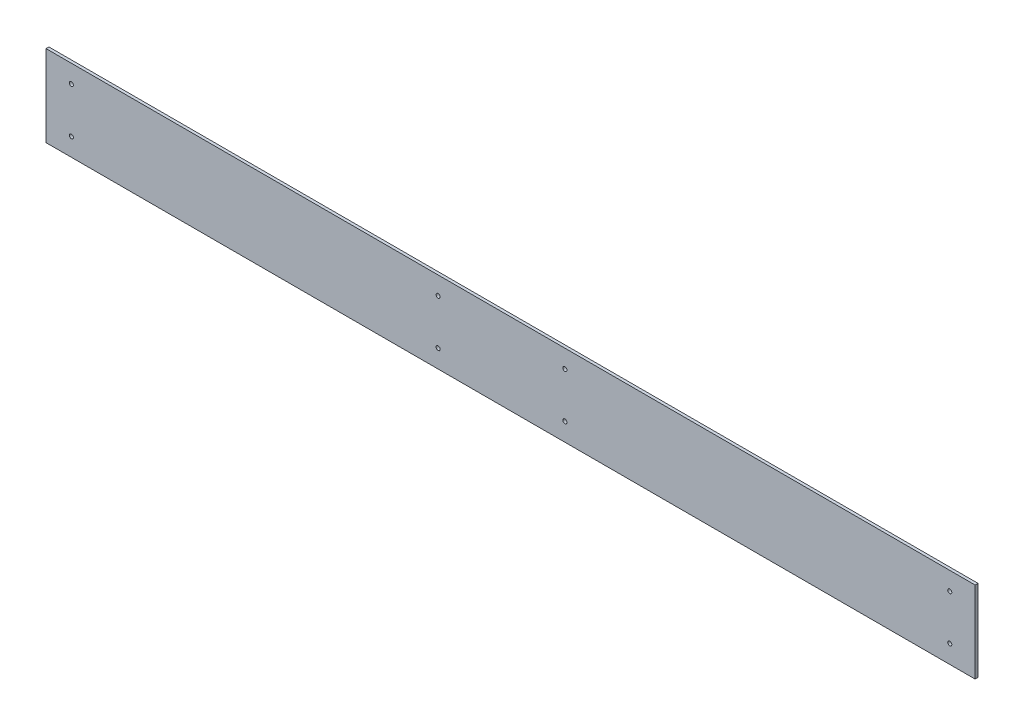
SolidWorks part; units mm, degrees
ref_plane "Front Plane" through (0, 0, 0) normal (0, 0, 1) x (1, 0, 0)
ref_plane "Top Plane" through (0, 0, 0) normal (0, 1, 0) x (1, 0, 0)
ref_plane "Right Plane" through (0, 0, 0) normal (1, 0, 0) x (0, 0, -1)
sketch "Sketch1" plane through (0, 0, 0) normal (0, 0, 1) x (1, 0, 0)
  line L1 (-513, -45) -> (513, -45)
  line L2 (-513, -45) -> (-513, 45)
  line L3 (-513, 45) -> (513, 45)
  line L4 (513, -45) -> (513, 45)
  line L5 (-513, -45) -> (513, 45) construction
  line L6 (-513, 45) -> (513, -45) construction
  point P0 (0, 0)
  dimension "D1" = 1026
  dimension "D2" = 90
extrude "Boss-Extrude1" add sketch "Sketch1" along normal blind 3.175
hole_wizard "M4 Clearance Hole1" positions "Sketch2" profile "Sketch4" hole size "M4" standard "ANSI Metric" end condition through all
sketch "Sketch2" plane through (0, 0, 3.175) normal (0, 0, 1) x (1, 0, 0)
  line L0 (-485, 25) -> (-485, -25)
  line L1 (513, 45) -> (-513, 45) construction
  line L2 (-513, -45) -> (513, -45) construction
  line L3 (-513, 45) -> (-513, -45) construction
  line L4 (0, -55) -> (0, 55) construction
  line L5 (485, 25) -> (485, -25)
  line L6 (-80, 25) -> (-80, -25)
  line L8 (60, 25) -> (60, -25)
  point P1 (-485, 25)
  point P2 (-485, -25)
  point P19 (485, -25)
  point P20 (485, 25)
  point P24 (-80, 25)
  point P25 (-80, -25)
  point P28 (60, 25)
  point P29 (60, -25)
  dimension "D1" = 20
  dimension "D2" = 20
  dimension "D3" = 28
  dimension "D4" = 433
  dimension "D5" = 140
sketch "Sketch4" plane through (-485, 25, 3.175) normal (1, 0, 0) x (0, -1, 0)
  line L0 (0, 0) -> (0, 3.175)
  line L1 (0, 3.175) -> (2.25, 3.175)
  line L2 (2.25, 3.175) -> (2.25, 0)
  line L5 (2.25, 0) -> (0, 0)
  line L11 (0, -6.35) -> (0, 107.95) construction
  dimension "Thru Hole Dia." = 4.5
  dimension "Thru Hole Depth" = 3.175
